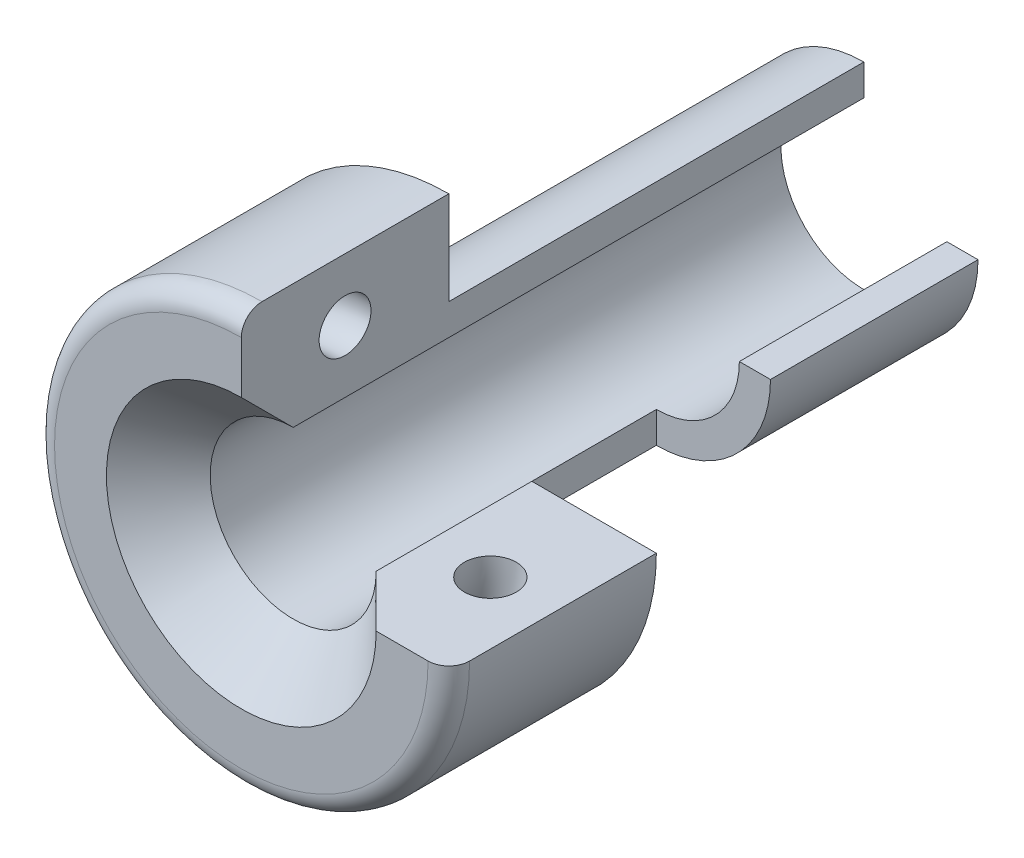
SolidWorks part; units mm, degrees
material "Brass"
ref_plane "Front Plane" through (0, 0, 0) normal (0, 0, 1) x (1, 0, 0)
ref_plane "Top Plane" through (0, 0, 0) normal (0, 1, 0) x (1, 0, 0)
ref_plane "Right Plane" through (0, 0, 0) normal (1, 0, 0) x (0, 0, -1)
sketch "Sketch6" plane through (0, 0, 0) normal (1, 0, 0) x (0, 0, -1)
  line L0 (20, 11) -> (20, 8)
  line L1 (0, 0) -> (72.5373, 0) construction
  line L2 (0, 8) -> (0, 20)
  line L3 (0, 20) -> (20, 20)
  line L4 (60, 8) -> (60, 11)
  line L7 (60, 11) -> (20, 11)
  line L8 (20, 20) -> (20, 11)
  line L11 (0, 8) -> (60, 8)
  line L13 (40, 11) -> (40, 8)
  circle A0 centre (10, 14) radius 2.5
  dimension "D8" = 5
  dimension "D1" = 20
  dimension "D4" = 22
  dimension "D5" = 60
  dimension "D6" = 14
  dimension "D7" = 10
  dimension "D9" = 20
revolve "Revolve3" add sketch "Sketch6" angle 270 about L1 region at (0, 9.5, -19.7668) region at (0, 9.5, -50) reverse direction yes
revolve "Revolve4" add sketch "Sketch6<3>" angle 180 about L1 region at (0, 9.5, -30) region at (0, 9.5, -50) reverse direction yes
sketch "Sketch6<3>" plane through (0, 0, 0) normal (1, 0, 0) x (0, 0, -1) same geometry as "Sketch6"
chamfer "Chamfer1" distance 5 angle 45 1 edges at (-5.6569, -5.6569, 0)
fillet "Fillet1" radius 2 1 edges at (-14.1421, -14.1421, 0)
